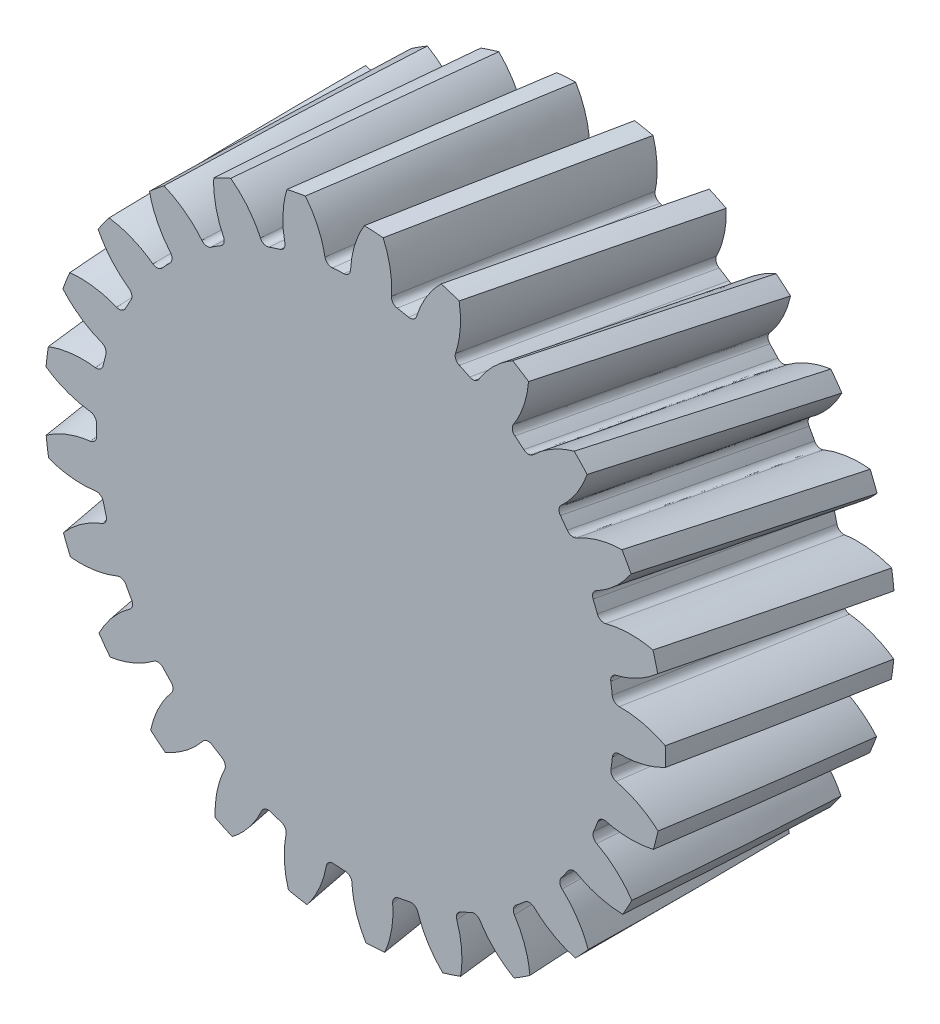
SolidWorks part; units mm, degrees
material "Plain Carbon Steel"
ref_plane "Front Plane" through (0, 0, 0) normal (0, 0, 1) x (1, 0, 0)
ref_plane "Top Plane" through (0, 0, 0) normal (0, 1, 0) x (1, 0, 0)
ref_plane "Right Plane" through (0, 0, 0) normal (1, 0, 0) x (0, 0, -1)
sketch "Sketch1" plane through (0, 0, 0) normal (0, 0, 1) x (1, 0, 0)
  circle A0 centre (0, 0) radius 25
  circle A1 centre (0, 0) radius 27
  circle A2 centre (0, 0) radius 22.5
  dimension "D1" = 50
  dimension "D2" = 54
  dimension "D3" = 4.5
extrude "Boss-Extrude1" add sketch "Sketch1" along normal mid plane 20 contours A1
sketch "Sketch2" plane through (0, 0, 0) normal (0, 0, 1) x (1, 0, 0)
  line L0 (0, 0) -> (0, 27) construction
  line L1 (-1.5698, 24.9507) -> (1.5698, 24.9507) construction
  line L2 (0, 0) -> (-1.072, 22.4744) construction
  line L3 (-2.6344, 27.8758) -> (0, 20.6378) construction
  line L4 (0, 0) -> (3.384, 26.7871) construction
  line L5 (1.5698, 24.9507) -> (4.6845, 24.5572) construction
  circle A0 centre (0, 0) radius 27 construction
  arc A1 (-3.3153, 27.803) -> (-1.072, 22.4744) centre (-9.4743, 22.0737) cw
  arc A2 (3.3153, 27.803) -> (1.072, 22.4744) centre (9.4743, 22.0737) ccw
  circle A3 centre (0, 0) radius 22.5 construction
  arc A4 (1.072, 22.4744) -> (-1.072, 22.4744) centre (0, 0) ccw
  circle A7 centre (0, 0) radius 25 construction
  circle A8 centre (0, 0) radius 28
  arc A9 (3.3153, 27.803) -> (-3.3153, 27.803) centre (0, 0) ccw
  circle A10 centre (0, 0) radius 27 construction
  dimension "D2" = 20
  dimension "D3" = 7.2
  dimension "D1" = 1
sketch "Sketch3" plane through (0, 0, 0) normal (0, 1, 0) x (1, 0, 0)
  line L0 (-1.7633, -10) -> (1.7633, 10)
  line L3 (-27, -10) -> (27, -10) construction
  line L4 (27, 10) -> (-27, 10) construction
  line L5 (0, -11) -> (0, 11) construction
  point P6 (0, 0)
  point P7 (-8.7267, -10)
  dimension "D1" = 10
curve "Curve1"
sketch "Sketch4" plane through (0, 0, 10) normal (0, 0, 1) x (0.9979, 0.0653, 0)
  line L0 (0, 0) -> (0, 27) construction
  line L1 (-1.5698, 24.9507) -> (1.5698, 24.9507) construction
  line L2 (0, 0) -> (-1.072, 22.4744) construction
  line L3 (-2.6344, 27.8758) -> (0, 20.6378) construction
  line L4 (0, 0) -> (3.384, 26.7871) construction
  line L5 (1.5698, 24.9507) -> (4.6845, 24.5572) construction
  arc A1 (-3.3153, 27.803) -> (-1.072, 22.4744) centre (-9.4743, 22.0737) cw
  arc A2 (3.3153, 27.803) -> (1.072, 22.4744) centre (9.4743, 22.0737) ccw
  arc A4 (1.072, 22.4744) -> (-1.072, 22.4744) centre (0, 0) ccw
  arc A9 (3.3153, 27.803) -> (-3.3153, 27.803) centre (0, 0) ccw
sketch "Sketch5" plane through (0, 0, -10) normal (0, 0, 1) x (0.9979, -0.0653, 0)
  line L0 (0, 0) -> (0, 27) construction
  line L1 (-1.5698, 24.9507) -> (1.5698, 24.9507) construction
  line L2 (0, 0) -> (-1.072, 22.4744) construction
  line L3 (-2.6344, 27.8758) -> (0, 20.6378) construction
  line L4 (0, 0) -> (3.384, 26.7871) construction
  line L5 (1.5698, 24.9507) -> (4.6845, 24.5572) construction
  arc A1 (-3.3153, 27.803) -> (-1.072, 22.4744) centre (-9.4743, 22.0737) cw
  arc A2 (3.3153, 27.803) -> (1.072, 22.4744) centre (9.4743, 22.0737) ccw
  arc A4 (1.072, 22.4744) -> (-1.072, 22.4744) centre (0, 0) ccw
  arc A9 (3.3153, 27.803) -> (-3.3153, 27.803) centre (0, 0) ccw
loft "Cut-Loft1" cut profiles "Sketch4", "Sketch2", "Sketch5" start constraint default end constraint default
fillet "Fillet1" radius 0.6 2 edges
pattern_circular "CirPattern2" count 25 over 360 about axis through (0, 0, 10) along (0, 0, -1) of "Cut-Loft1", "Fillet1" reverse direction yes
equation "\"module\"= 2mm"
equation "\"Number of teeth\"= 25"
equation "\"D2@Sketch1\"=(\"Number of teeth\" + 2) * \"module\""
equation "\"D3@Sketch1\"=\"module\" * if( \"module\"=>1.25,2.25,2.4)"
equation "\"D3@Sketch2\"=180/\"Number of teeth\""
